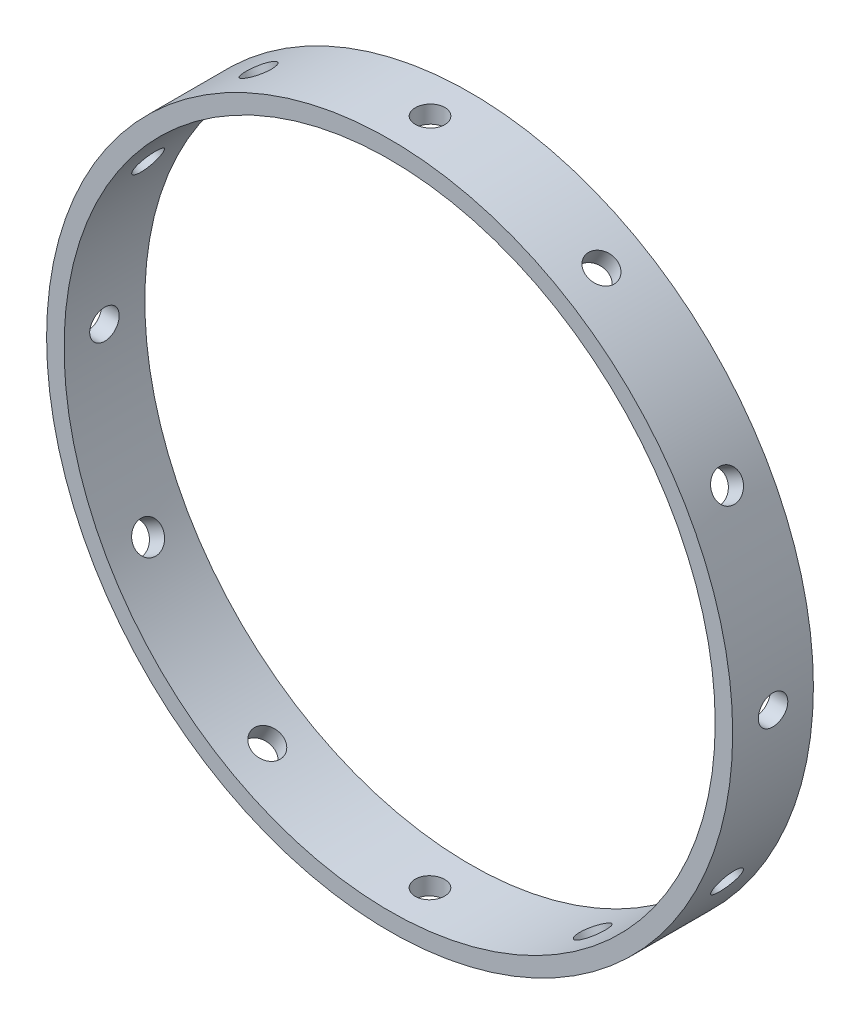
SolidWorks part; units mm, degrees
ref_plane "Front Plane" through (0, 0, 0) normal (0, 0, 1) x (1, 0, 0)
ref_plane "Top Plane" through (0, 0, 0) normal (0, 1, 0) x (1, 0, 0)
ref_plane "Right Plane" through (0, 0, 0) normal (1, 0, 0) x (0, 0, -1)
sketch "Sketch1" plane through (0, 0, 0) normal (0, 0, 1) x (1, 0, 0)
  circle A0 centre (0, 0) radius 76.835
  circle A1 centre (0, 0) radius 80.9625
  dimension "D1" = 153.67
  dimension "D2" = 161.925
extrude "Boss-Extrude1" add sketch "Sketch1" along normal blind 19.05
sketch "Sketch2" plane through (0, 0, 0) normal (0, 1, 0) x (1, 0, 0)
  line L0 (76.835, 0) -> (-76.835, 0) construction
  line L1 (0, -2.0807) -> (0, -15.8358) construction
  circle A0 centre (0, -9.525) radius 3.4782
  dimension "D1" = 9.525
extrude "Cut-Extrude1" cut sketch "Sketch2" against normal through all
ref_axis "Axis1" through (0, 0, 2.0807) along (0, 0, 1)
pattern_circular "CirPattern1" count 12 over 360 about axis through (0, 0, 2.0807) along (0, 0, 1) of "Cut-Extrude1"
